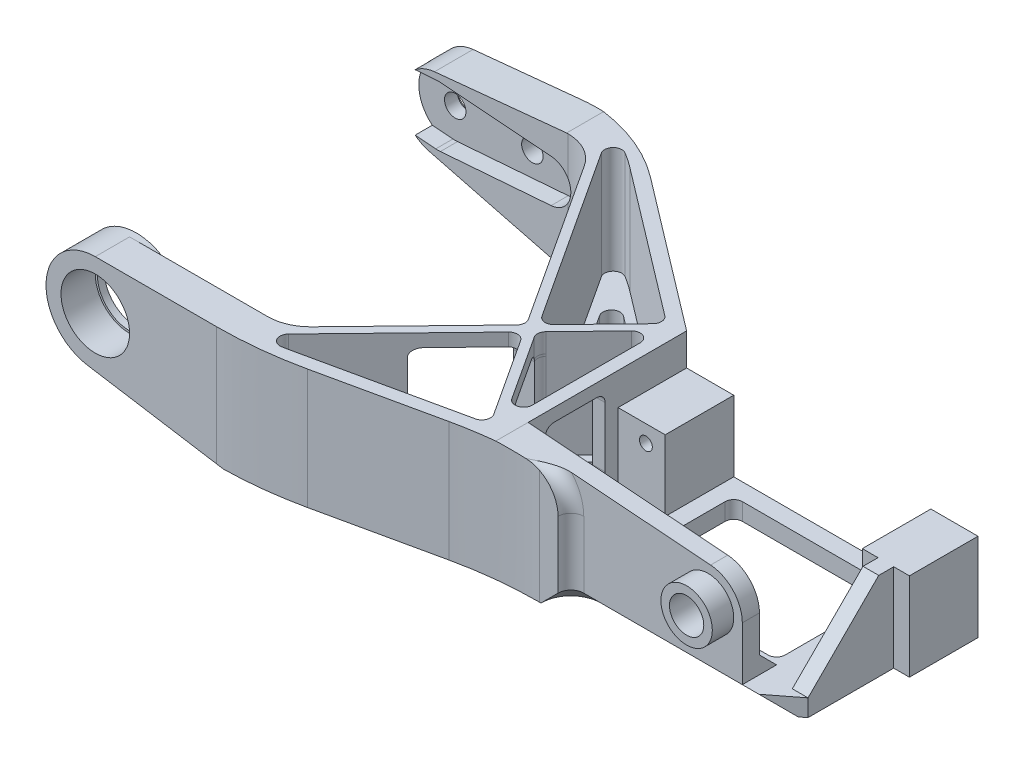
SolidWorks part; units mm, degrees
material "ABS"
ref_plane "Front Plane" through (0, 0, 0) normal (0, 0, 1) x (1, 0, 0)
ref_plane "Top Plane" through (0, 0, 0) normal (0, 1, 0) x (1, 0, 0)
ref_plane "Right Plane" through (0, 0, 0) normal (1, 0, 0) x (0, 0, -1)
sketch "Sketch1" plane through (0, 0, 0) normal (0, 1, 0) x (1, 0, 0)
  line L0 (0, 0) -> (0, -22)
  line L1 (0, 0) -> (34, 0)
  line L2 (34, 0) -> (34, -22)
  line L3 (34, -22) -> (0, -22)
  line L4 (0, -18) -> (34, -18) construction
  line L5 (6, -16) -> (28, -16) construction
  line L6 (6, -16) -> (6, 8) construction
  line L7 (6, 8) -> (28, 8) construction
  line L8 (28, -16) -> (28, 8) construction
  line L9 (1, 2) -> (33, 2) construction
  line L10 (1, 2) -> (1, 0) construction
  line L11 (1, 0) -> (33, 0) construction
  line L12 (33, 2) -> (33, 0) construction
  line L13 (21.5, 15.5) -> (21.5, -23) construction
  point P13 (17, 2)
  point P14 (17, 8)
  point P15 (17, -16)
  point P16 (17, 0)
  dimension "D1" = 22
  dimension "D2" = 32
  dimension "D3" = 22
  dimension "D4" = 16
  dimension "D5" = 24
  dimension "D6" = 2
  dimension "D7" = 34
  dimension "D8" = 4
  dimension "D9" = 6.5
  dimension "D10" = 15.5
  dimension "D11" = 1
extrude "Boss-Extrude1" add sketch "Sketch1" along normal blind 2
sketch "Sketch2" plane through (0, 2, 0) normal (0, 1, 0) x (1, 0, 0)
  line L0 (34, -22) -> (34, 0) construction
  line L1 (0, 0) -> (5.5, 0)
  line L2 (0, 0) -> (0, -8)
  line L3 (0, -8) -> (5.5, -8)
  line L4 (5.5, 0) -> (5.5, -8)
  line L5 (34, 0) -> (28.5, 0)
  line L6 (34, 0) -> (34, -8)
  line L7 (34, -8) -> (28.5, -8)
  line L8 (28.5, 0) -> (28.5, -8)
  line L9 (0, -22) -> (34, -22)
  line L10 (0, -22) -> (0, -18)
  line L11 (0, -18) -> (34, -18)
  line L12 (34, -22) -> (34, -18)
  dimension "D1" = 5.5
  dimension "D2" = 4
  dimension "D3" = 8
  dimension "D4" = 23
extrude "Boss-Extrude2" add sketch "Sketch2" along normal blind 12
sketch "Sketch3" plane through (0, 0, 22) normal (0, 0, 1) x (1, 0, 0)
  line L0 (28.5, 14) -> (28.5, 2) construction
  line L1 (34, 2) -> (0, 2) construction
  circle A0 centre (23, 8.25) radius 3
  dimension "D1" = 5.5
  dimension "D2" = 6.25
  dimension "D3" = 6
extrude "Boss-Extrude3" add sketch "Sketch3" along normal blind 1
sketch "Sketch4" plane through (0, 0, 23) normal (0, 0, 1) x (1, 0, 0)
  circle A0 centre (23, 8.25) radius 2
  circle A1 centre (23, 8.25) radius 3 construction
  dimension "D1" = 4
extrude "Cut-Extrude1" cut sketch "Sketch4" against normal blind 11
sketch "Sketch5" plane through (0, 0, 0) normal (0, 0, -1) x (-1, 0, 0)
  line L0 (-17, 13.8331) -> (-17, 2) construction
  line L1 (-28.5, 2) -> (-5.5, 2) construction
  circle A0 centre (-30.75, 8.25) radius 0.75
  circle A1 centre (-3.25, 8.25) radius 0.75
  circle A2 centre (-23, 8.25) radius 2 construction
  circle A3 centre (-23, 8.25) radius 2 construction
  dimension "D1" = 1.5
  dimension "D2" = 27.5
  dimension "D3" = 13.75
extrude "Cut-Extrude2" cut sketch "Sketch5" against normal blind 11
sketch "Sketch7" plane through (0, 0, 0) normal (0, -1, 0) x (1, 0, 0)
  line L0 (-50.5, 23) -> (-27, 23)
  line L1 (-27, 23) -> (-27, -15)
  line L2 (-27, -15) -> (-50.5, -15)
  line L3 (-43.5, 33.241) -> (-43.5, -32.1535) construction
  line L4 (21.5, -15.5) -> (21.5, 23) construction
  line L5 (-50.5, 23) -> (-50.5, 27)
  line L6 (-50.5, 27) -> (-23, 27)
  line L7 (-23, 27) -> (0, 22)
  line L8 (0, 0) -> (-23, -17.5)
  line L9 (-23, -17.5) -> (-50.5, -17.5)
  line L10 (-50.5, -17.5) -> (-50.5, -15)
  line L11 (0, 22) -> (0, 0)
  dimension "D1" = 65
  dimension "D2" = 16.5
  dimension "D3" = 4
  dimension "D4" = 7
  dimension "D5" = 4
  dimension "D6" = 2.5
  dimension "D7" = 44.5
extrude "Boss-Extrude4" add sketch "Sketch7" against normal blind 14
sketch "Sketch8" plane through (0, 0, -17.5) normal (0, 0, -1) x (-1, 0, 0)
  circle A0 centre (42, 8.25) radius 1.25
  circle A1 centre (-23, 8.25) radius 2 construction
  circle A2 centre (-23, 8.25) radius 2 construction
  circle A3 centre (33, 8.25) radius 1.25
  dimension "D1" = 65
  dimension "D2" = 2.5
  dimension "D3" = 9
extrude "Cut-Extrude3" cut sketch "Sketch8" against normal blind 14
sketch "Sketch9" plane through (0, 0, 27) normal (0, 0, 1) x (1, 0, 0)
  circle A0 centre (-42, 8.25) radius 4
  circle A2 centre (-42, 8.25) radius 1.25 construction
  dimension "D1" = 8
extrude "Cut-Extrude4" cut sketch "Sketch9" against normal blind 14
sketch "Sketch10" plane through (0, 0, -15) normal (0, 0, 1) x (1, 0, 0)
  line L0 (-27, 14) -> (-42.4171, 12.4795)
  line L1 (-27, 0) -> (-43.0595, 4.1342)
  line L2 (-27, 14) -> (-50.5, 14)
  line L3 (-50.5, 14) -> (-50.5, 0)
  line L4 (-50.5, 0) -> (-27, 0)
  arc A0 (-42.4171, 12.4795) -> (-43.0595, 4.1342) centre (-42, 8.25) ccw
  circle A1 centre (-42, 8.25) radius 1.25 construction
  dimension "D1" = 3
extrude "Cut-Extrude5" cut sketch "Sketch10" against normal blind 14
sketch "Sketch11" plane through (0, 0, 23) normal (0, 0, -1) x (-1, 0, 0)
  line L0 (50.5, 14) -> (27, 14) construction
  line L1 (27, 0) -> (42.9178, 2.5737)
  line L2 (42, 14) -> (53.108, 14)
  line L3 (53.108, 14) -> (50.7525, 0)
  line L4 (50.7525, 0) -> (27, 0)
  arc A0 (42.9178, 2.5737) -> (42, 14) centre (42, 8.25) ccw
  dimension "D1" = 10
extrude "Cut-Extrude6" cut sketch "Sketch11" against normal blind 14
sketch "Sketch12" plane through (0, 14, 0) normal (0, 1, 0) x (1, 0, 0)
  line L0 (0, 0.013) -> (0, -22) construction
  line L1 (0, -22) -> (-23, -27) construction
  line L2 (-23, -27) -> (-27, -27) construction
  line L3 (-23, -27) -> (-42, -27) construction
  line L4 (-27, -27) -> (-27, 17.5) construction
  line L5 (-27, 17.5) -> (-23, 17.5) construction
  line L6 (-23, 17.5) -> (0, 0.013) construction
  line L7 (-27, -23) -> (-27, 15) construction
  line L8 (-1.5, -0.7308) -> (-1.5, -20.7911)
  line L9 (-1.5, -20.7911) -> (-23.1612, -25.5)
  line L10 (-23.1612, -25.5) -> (-25.5, -25.5)
  line L11 (-25.5, -25.5) -> (-25.5, 16)
  line L12 (-25.5, 16) -> (-23.5055, 16)
  line L13 (-23.5055, 16) -> (-1.5, -0.7308)
  line L14 (0, -8) -> (0, -18) construction
  dimension "D1" = 1.5
extrude "Cut-Extrude7" cut sketch "Sketch12" against normal offset from surface (12.5 mm away) 1.5 up to face at (-8.6, 0, 7.1)
sketch "Sketch13" plane through (0, 1.5, 0) normal (0, 1, 0) x (1, 0, 0)
  line L0 (-1.5, -0.7308) -> (-25.5, -25.5) construction
  line L1 (-25.5, 16) -> (-25.5, -25.5) construction
  line L2 (-25.5, -25.5) -> (-23.1612, -25.5) construction
  line L3 (-1.0812, -20.5179) -> (-25.0812, 16.2732)
  line L4 (-1.5, -20.7911) -> (-25.5, 16) construction
  line L5 (-1.8591, -0.3829) -> (-25.8591, -25.1521)
  line L6 (-1.9188, -21.0642) -> (-25.9188, 15.7268)
  line L7 (-1.1409, -1.0788) -> (-25.1409, -25.8479)
  line L8 (-25.9188, 15.7268) -> (-25.0812, 16.2732)
  line L9 (-25.1409, -25.8479) -> (-25.8591, -25.1521)
  line L10 (-1.0812, -20.5179) -> (-1.9188, -21.0642)
  line L11 (-1.1409, -1.0788) -> (-1.8591, -0.3829)
  line M3 (-1.5, -0.7308) -> (-23.5055, 16)
  line M4 (-23.5055, 16) -> (-25.5, 16)
  line M5 (-25.5, 16) -> (-25.5, -25.5)
  line M6 (-25.5, -25.5) -> (-23.1612, -25.5)
  line M7 (-23.1612, -25.5) -> (-1.5, -20.7911)
  line M8 (-1.5, -20.7911) -> (-1.5, -0.7308)
  dimension "D1" = 0.5
  dimension "D2" = 0.5
extrude "Boss-Extrude5" add sketch "Sketch13" along normal up to surface (12.5 mm away) contours L7 L6 L5 M5 M6 | L7 L3 L5 L6 | L3 L7 L6 M7 M8 | L7 L5 L3 M8 M3 | L6 L5 L3 M4 M5 region at (-5.3366, 1.5, 14.9136) region at (-9.3207, 1.5, 8.8022) region at (-5.2827, 1.5, 4.6322) region at (-17.4756, 1.5, -3.7001) region at (-17.5025, 1.5, 17.2452) up to face at (-16.7778, 14, 6.7536)
sketch "Sketch14" plane through (0, 1.5, 0) normal (0, 1, 0) x (1, 0, 0)
  line L0 (-25.5, -24.7815) -> (-25.5, 15.0849) construction
  line L1 (-25.5, 15.0849) -> (-9.9576, -8.741) construction
  line L2 (-9.9576, -8.741) -> (-25.5, -24.7815) construction
  line L3 (-2.0228, -20.9047) -> (-9.3974, -9.5998) construction
  line L4 (-9.3974, -9.5998) -> (-24.8038, -25.5) construction
  line L5 (-24.8038, -25.5) -> (-23.1612, -25.5) construction
  line L6 (-23.1612, -25.5) -> (-2.0228, -20.9047) construction
  line L7 (-1.5, -19.8759) -> (-1.5, -1.4494) construction
  line L8 (-1.5, -1.4494) -> (-8.6838, -8.8634) construction
  line L9 (-8.6838, -8.8634) -> (-1.5, -19.8759) construction
  line L10 (-9.2441, -8.0046) -> (-24.903, 16) construction
  line L11 (-24.903, 16) -> (-23.5055, 16) construction
  line L12 (-23.5055, 16) -> (-1.9009, -0.426) construction
  line L13 (-1.9009, -0.426) -> (-9.2441, -8.0046) construction
  line L14 (-24.5, -22.3124) -> (-24.5, 11.7216)
  line L15 (-24.5, 11.7216) -> (-11.2314, -8.6186)
  line L16 (-11.2314, -8.6186) -> (-24.5, -22.3124)
  line L17 (-3.6532, -20.2358) -> (-9.5507, -11.1951)
  line L18 (-9.5507, -11.1951) -> (-22.2219, -24.2725)
  line L19 (-22.2219, -24.2725) -> (-22.2219, -24.2725)
  line L20 (-22.2219, -24.2725) -> (-3.6532, -20.2358)
  line L21 (-2.5, -16.5127) -> (-2.5, -3.9185)
  line L22 (-2.5, -3.9185) -> (-7.41, -8.9858)
  line L23 (-7.41, -8.9858) -> (-2.5, -16.5127)
  line L24 (-9.0908, -6.4093) -> (-22.2836, 13.8148)
  line L25 (-22.2836, 13.8148) -> (-22.2836, 13.8148)
  line L26 (-22.2836, 13.8148) -> (-3.4035, -0.5398)
  line L27 (-3.4035, -0.5398) -> (-9.0908, -6.4093)
  dimension "D1" = 1
extrude "Cut-Extrude8" cut sketch "Sketch14" against normal blind 1.5
sketch "Sketch15" plane through (0, 0, 22) normal (0, 0, 1) x (1, 0, 0)
  line L0 (0, 14) -> (23.3015, 12.2386)
  line L1 (27, 8.25) -> (27, 2)
  line L2 (27, 2) -> (34, 2)
  line L3 (34, 14) -> (34, 0) construction
  line L4 (34, 2) -> (34, 14)
  line L5 (34, 14) -> (0, 14)
  line L6 (0, 0) -> (34, 0) construction
  arc A0 (27, 8.25) -> (23.3015, 12.2386) centre (23, 8.25) ccw
  circle A1 centre (23, 8.25) radius 3 construction
  dimension "D1" = 1
  dimension "D2" = 2
extrude "Cut-Extrude9" cut sketch "Sketch15" against normal up to next
sketch "Sketch21" plane through (0, 0, -15) normal (0, 0, 1) x (1, 0, 0)
  line L0 (-29, 8.25) -> (-42, 8.25) construction
  line L1 (-42, 8.25) -> (-55, 8.25) construction
  line L2 (-28.8077, 5.7574) -> (-41.7308, 4.7604)
  line L3 (-28.8077, 10.7426) -> (-41.7308, 11.7396)
  line L4 (-42.2692, 11.7396) -> (-55.1923, 10.7426)
  line L5 (-27, 0) -> (-27, 14)
  line L6 (-55.1923, 5.7574) -> (-42.2692, 4.7604)
  line L7 (-27, 14) -> (-27, 0) construction
  line L8 (-27, 14) -> (-42.4171, 12.4795)
  line L10 (-43.0595, 4.1342) -> (-27, 0)
  arc A0 (-41.7308, 11.7396) -> (-42.2692, 11.7396) centre (-42, 8.25) ccw
  arc A1 (-28.8077, 5.7574) -> (-28.8077, 10.7426) centre (-29, 8.25) ccw
  arc A2 (-55.1923, 10.7426) -> (-55.1923, 5.7574) centre (-55, 8.25) ccw
  arc A3 (-42.2692, 4.7604) -> (-41.7308, 4.7604) centre (-42, 8.25) ccw
  arc A4 (-43.0595, 4.1342) -> (-42.4171, 12.4795) centre (-42, 8.25) cw
  line M11 (-27, 14) -> (-42.4171, 12.4795)
  arc M12 (-42.4171, 12.4795) -> (-43.0595, 4.1342) centre (-42, 8.25) ccw
  line M13 (-43.0595, 4.1342) -> (-27, 0)
  line M14 (-27, 0) -> (-27, 14)
  dimension "D1" = 13
  dimension "D2" = 7
  dimension "D3" = 5
extrude "Boss-Extrude7" add sketch "Sketch21" along normal blind 2 contours A3 L6 A1 L2 M12 M13 M14 | A1 L4 A0 L3 M14 M11 M12 region at (-32.8976, 3.5101, -15) region at (-33.2832, 12.2017, -15)
fillet "Fillet2" radius 45 2 edges at (-23, 7, 27) (0, 7, 22)
fillet "Fillet3" radius 20 1 edges at (-23, 7, -17.5)
sketch "Sketch17" plane through (34, 0, 0) normal (1, 0, 0) x (0, 0, -1)
  line L0 (-8, 2) -> (-8, 12)
  line L1 (-8, 14) -> (-8, 2) construction
  line L2 (-8, 12) -> (-18, 2)
  line L3 (-22, 2) -> (-8, 2) construction
  line L4 (-18, 2) -> (-8, 2)
  dimension "D1" = 10
extrude "Boss-Extrude6" add sketch "Sketch17" against normal blind 1.8333 from offset 1.8333 offset against normal yes
sketch "Sketch18" plane through (0, 2, 0) normal (0, 1, 0) x (1, 0, 0)
  line L0 (27, -22) -> (32.1667, -18)
  line L1 (32.1667, -18) -> (32.1667, -8)
  line L2 (32.1667, -8) -> (34, -8)
  line L3 (34, -8) -> (34, -22)
  line L4 (34, -22) -> (27, -22)
extrude "Cut-Extrude10" cut sketch "Sketch18" against normal through all
sketch "Sketch19" plane through (0, 2, 0) normal (0, 1, 0) x (1, 0, 0)
  line L0 (28.5, 0) -> (5.5, 0) construction
  line L1 (5.5, 0) -> (0, 0) construction
  line L2 (5.5, -8) -> (5.5, 0) construction
  line L3 (5.5, 0) -> (5.5, -18) construction
  line L4 (27, -18) -> (0, -18) construction
  line L5 (5.5, -18) -> (28.5, -18) construction
  line L6 (28.5, -18) -> (28.5, 0) construction
  line L7 (26.5, -2) -> (7.5, -2)
  line L8 (7.5, -2) -> (7.5, -16)
  line L9 (7.5, -16) -> (26.5, -16)
  line L10 (26.5, -16) -> (26.5, -2)
  dimension "D1" = 2
extrude "Cut-Extrude11" cut sketch "Sketch19" against normal through all
sketch "Sketch20" plane through (0, 0, 0) normal (1, 0, 0) x (0, 0, -1)
  line L0 (-8, 2) -> (-18, 2) construction
  line L1 (-18, 2) -> (-18, 14) construction
  line L2 (-18, 14) -> (-8, 14) construction
  line L3 (-8, 14) -> (-8, 2) construction
  line L4 (-9.5, 3.5) -> (-16.5, 3.5)
  line L5 (-16.5, 3.5) -> (-16.5, 12.5)
  line L6 (-16.5, 12.5) -> (-9.5, 12.5)
  line L7 (-9.5, 12.5) -> (-9.5, 3.5)
  dimension "D1" = 1.5
extrude "Cut-Extrude12" cut sketch "Sketch20" against normal blind 31.6667
fillet "Fillet4" radius 20 2 edges at (-23.5055, 7.75, -16) (-23.1612, 7.75, 25.5)
sketch "Sketch27" plane through (0, 14, 0) normal (0, 1, 0) x (1, 0, 0)
  line L0 (27, -18) -> (27, -22) construction
  line L1 (0, -18) -> (27, -18)
  line L2 (0, -18) -> (0, -18.5)
  line L3 (0, -18.5) -> (27, -18.5)
  line L4 (27, -18) -> (27, -18.5)
  dimension "D1" = 0.5
extrude "Cut-Extrude15" cut sketch "Sketch27" against normal up to surface (12 mm away) up to face at (17, 2, 9)
fillet "Fillet6" radius 1 18 edges at (-0.75, 12.5, 9.5) (-9.4808, 12.5, 9.5) (-26.25, 12.5, 9.5) (-0.75, 3.5, 9.5) (-9.4808, 3.5, 9.5) (-26.25, 3.5, 9.5) (-26.25, 12.5, 16.5) (-16.7795, 12.5, 16.5) (-0.75, 12.5, 16.5) (-4.2992, 12.5, 16.5) (-26.25, 3.5, 16.5) (-16.7795, 3.5, 16.5) (-4.2992, 3.5, 16.5) (-0.75, 3.5, 16.5) (26.5, 1, 16) (26.5, 1, 2) (7.5, 1, 2) (7.5, 1, 16)
sketch "Sketch22" plane through (0, 0, 23) normal (0, 0, -1) x (-1, 0, 0)
  circle A0 centre (42, 8.25) radius 3.75
  circle A1 centre (42, 8.25) radius 5.75
  dimension "D1" = 7.5
extrude "Boss-Extrude8" add sketch "Sketch22" along normal blind 0.8
sketch "Sketch23" plane through (0, 0, 0) normal (0, 0, -1) x (-1, 0, 0)
  line L0 (0, 14) -> (0, 0) construction
  line L1 (-34, 14) -> (0, 14)
  line L2 (-34, 14) -> (-34, 10.25)
  line L3 (-34, 10.25) -> (0, 10.25)
  line L4 (0, 14) -> (0, 10.25)
  circle A0 centre (-30.75, 8.25) radius 0.75 construction
  dimension "D1" = 2
extrude "Cut-Extrude13" cut sketch "Sketch23" against normal blind 10.8
sketch "Sketch24" plane through (0, 0, 0) normal (0, -1, 0) x (1, 0, 0)
  line L0 (46.689, 6) -> (-57.6039, 6) construction
  line L1 (-27.8348, 27) -> (-42, 27) construction
  line L2 (-29.7436, -17.5) -> (-42.4171, -17.5) construction
  line L3 (26, 23) -> (20, 23) construction
  dimension "D1" = 21
  dimension "D2" = 23.5
  dimension "D3" = 17
sketch "Sketch25" plane through (0, 0, 22) normal (0, 0, 1) x (1, 0, 0)
  line L1 (23.3015, 12.2386) -> (3.3015, 13.7504)
  line L3 (27, 0) -> (7, 0)
  line L4 (4.8348, 0) -> (27, 0) construction
  line L5 (7, 0) -> (7, 9.7618)
  line L6 (4.8348, 13.6345) -> (23.3015, 12.2386) construction
  line L7 (27, 8.25) -> (27, 2)
  line L8 (27, 2) -> (30.3591, 2)
  line L9 (30.3591, 2) -> (30.3591, 0)
  line L10 (30.3591, 0) -> (7, 0)
  circle A0 centre (23, 8.25) radius 3
  arc A1 (23.3015, 12.2386) -> (27, 8.25) centre (23, 8.25) cw
  arc A2 (7, 9.7618) -> (3.3015, 13.7504) centre (3, 9.7618) ccw
  circle A3 centre (23, 8.25) radius 3 construction
  circle M8 centre (23, 8.25) radius 3
  line M9 (4.8348, 0) -> (27, 0)
  line M10 (27, 0) -> (27, 2)
  line M11 (27, 2) -> (27, 8.25)
  arc M12 (27, 8.25) -> (23.3015, 12.2386) centre (23, 8.25) ccw
  line M13 (23.3015, 12.2386) -> (4.8348, 13.6345)
  line M14 (4.8348, 13.6345) -> (4.8348, 0)
  dimension "D1" = 4
  dimension "D2" = 4
  dimension "D3" = 20
extrude "Cut-Extrude14" cut sketch "Sketch25" against normal offset from surface 2.5 and the other way blind 10 contours A2 L5 M9 M10 M11 M12 M13 M14 M8 | A2 L1 M14 | L10 L9 L8 M10 region at (15.7802, 6.1432, 22) region at (4.4564, 13.5686, 22) region at (28.6796, 1, 22) up to face at (25, 8.25, 23)
fillet "Fillet7" radius 1.5 2 edges at (5.9331, 12.4816, 20.5) (7, 4.8809, 20.5)
chamfer "Chamfer1" distance 2 angle 45 3 edges at (7.4393, 0, 20.9393) (18.7188, 0, 20.5) (13.5, 2, 18.5)
sketch "Sketch28" plane through (0, 0, -17.5) normal (0, 0, -1) x (-1, 0, 0)
  circle A0 centre (42, 8.25) radius 2.5
  dimension "D1" = 5
extrude "Cut-Extrude16" cut sketch "Sketch28" against normal blind 1
sketch "Sketch29" plane through (0, 14, 0) normal (0, 1, 0) x (1, 0, 0)
  line L0 (-27, -23) -> (-23.7738, -23)
  line L1 (-9.9576, -8.741) -> (-25.5, -24.7815) construction
  line L2 (-23.7738, -23) -> (-24.14, 13)
  line L3 (-9.9576, -8.741) -> (-25.5, 15.0849) construction
  line L4 (-24.14, 13) -> (-27, 13)
  line L5 (-27, 13) -> (-27, -23)
extrude "Cut-Extrude17" cut sketch "Sketch29" against normal blind 20
sketch "Sketch30" plane through (0, 14, 0) normal (0, 1, 0) x (1, 0, 0)
  line L0 (-25.5, -23) -> (-23.7738, -23)
  line L1 (-23.7738, -23) -> (-25.5, -24.7815)
  line L2 (-25.5, -24.7815) -> (-25.5, -23)
  line L3 (-25.5, 15.0849) -> (-25.5, 13)
  line L4 (-25.5, 13) -> (-24.14, 13)
  line L5 (-24.14, 13) -> (-25.5, 15.0849)
extrude "Boss-Extrude9" add sketch "Sketch30" against normal up to surface (12.5 mm away) up to face at (-25.0467, 1.5, -13.695)
sketch "Sketch31" plane through (0, 1.5, 0) normal (0, 1, 0) x (1, 0, 0)
  line L0 (-24.1211, 11.1407) -> (-25.3339, 13)
  line L1 (-24.14, 13) -> (-27, 13) construction
  line L2 (-25.3339, 13) -> (-24.14, 13)
  line L3 (-24.14, 13) -> (-24.1211, 11.1407)
  line L4 (-23.7883, -21.5779) -> (-25.1663, -23)
  line L5 (-42, -23) -> (-23.7738, -23) construction
  line L6 (-25.1663, -23) -> (-23.7738, -23)
  line L7 (-23.7738, -23) -> (-23.7883, -21.5779)
  line L8 (-23.7883, -21.5779) -> (-11.2314, -8.6186) construction
  line L9 (-11.2314, -8.6186) -> (-24.1211, 11.1407) construction
extrude "Boss-Extrude10" add sketch "Sketch31" against normal up to surface (1.5 mm away) up to face at (-3.5226, 0, 9.4262)
fillet "Fillet8" radius 1 21 edges at (-22.2219, 0.75, 24.2725) (-24.8038, 7.75, 25.5) (-7.41, 0.75, 8.9858) (-8.6838, 7.75, 8.8634) (-1.5, 7.75, 19.8759) (-2.5, 0.75, 16.5127) (-1.5, 7.75, 1.4494) (-2.5, 0.75, 3.9185) (-9.5507, 0.75, 11.1951) (-9.3974, 2.7822, 9.5998) (-2.0228, 7.75, 20.9047) (-3.6532, 0.75, 20.2358) (-9.9576, 7.75, 8.741) (-11.2314, 0.75, 8.6186) (-1.9009, 7.75, 0.426) (-3.4035, 0.75, 0.5398) (-9.0908, 0.75, 6.4093) (-9.2441, 7.75, 8.0046) (-22.2836, 0.75, -13.8148) (-24.903, 7.75, -16) (-9.3974, 12.9678, 9.5998)
fillet "Fillet9" radius 5 2 edges at (-25.1663, 0.75, 23) (-25.3339, 0.75, -13)
fillet "Fillet10" radius 5 2 edges at (-24.14, 7.75, -13) (-23.7738, 7.75, 23)
sketch "Sketch32" plane through (0, 0, -13) normal (0, 0, 1) x (1, 0, 0)
  circle A0 centre (-29, 8.25) radius 2.5
  arc A1 (-28.8077, 5.7574) -> (-27, 6.75) centre (-29, 8.25) ccw construction
extrude "Cut-Extrude18" cut sketch "Sketch32" against normal up to surface (2 mm away) and the other way blind 20 up to face at (-37.0324, 8.25, -15)
equation "\"D3@Sketch5\"=\"D2@Sketch5\"/2"
equation "\"D1@Sketch13\"=\"D2@Sketch13\""
equation "\"D1@Sketch25\"=\"D2@Sketch25\""
